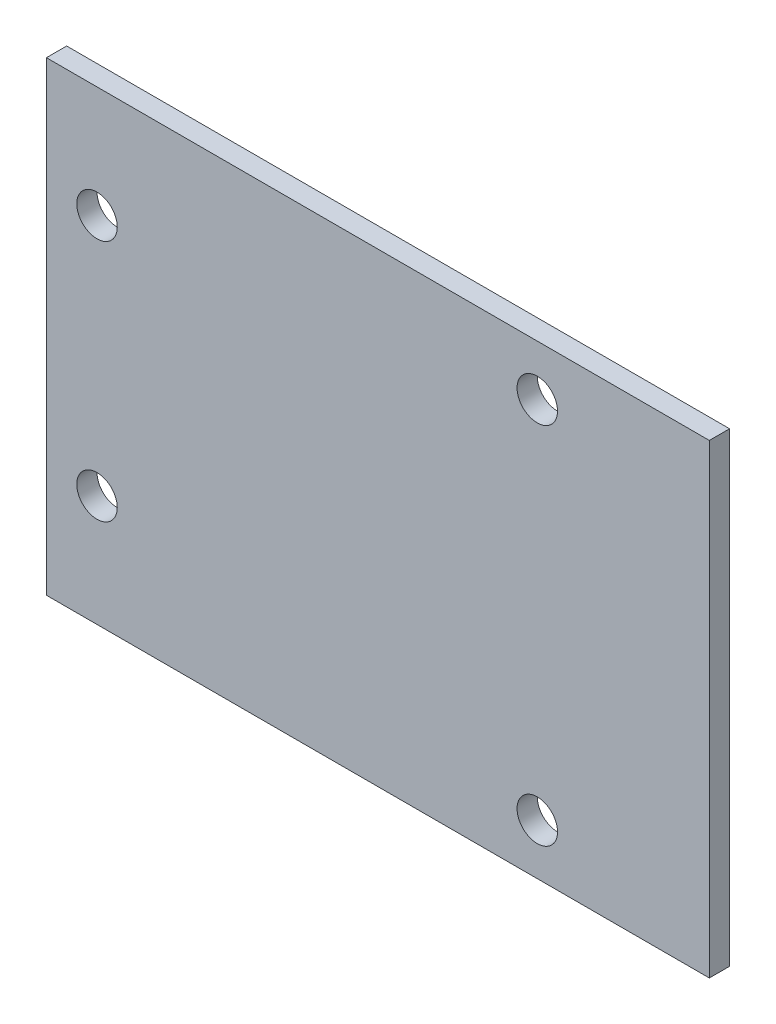
SolidWorks part; units mm, degrees
ref_plane "Plan de face" through (0, 0, 0) normal (0, 0, 1) x (1, 0, 0)
ref_plane "Plan de dessus" through (0, 0, 0) normal (0, 1, 0) x (1, 0, 0)
ref_plane "Plan de droite" through (0, 0, 0) normal (1, 0, 0) x (0, 0, -1)
sketch "Esquisse1" plane through (0, 0, 0) normal (0, 0, 1) x (1, 0, 0)
  line L1 (0, 0) -> (65.5, 0)
  line L2 (0, 0) -> (0, 46)
  line L3 (0, 46) -> (65.5, 46)
  line L4 (65.5, 0) -> (65.5, 46)
  dimension "D1" = 46
  dimension "D2" = 65.5
extrude "Boss.-Extru.1" add sketch "Esquisse1" along normal blind 2
sketch "Esquisse2" plane through (0, 0, 2) normal (0, 0, 1) x (1, 0, 0)
  line L1 (0, 0) -> (65.5, 0) construction
  line L2 (65.5, 46) -> (0, 46) construction
  line L3 (0, 46) -> (0, 0) construction
  circle A0 centre (5, 11) radius 2
  circle A1 centre (5, 35) radius 2
  circle A2 centre (48.5, 41) radius 2
  circle A3 centre (48.5, 5) radius 2
  dimension "D1" = 4
  dimension "D2" = 48.5
  dimension "D3" = 5
  dimension "D4" = 11
  dimension "D5" = 11
  dimension "D6" = 5
  dimension "D7" = 5
extrude "Enlèv. mat.-Extru.1" cut sketch "Esquisse2" against normal through all
